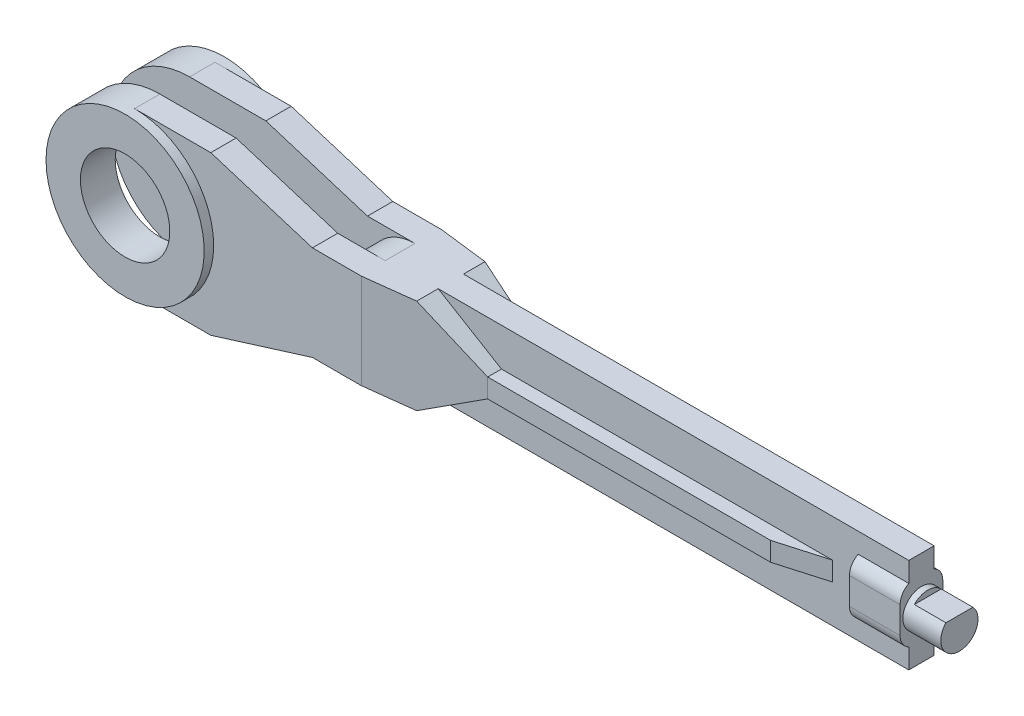
SolidWorks part; units mm, degrees
ref_plane "Front Plane" through (0, 0, 0) normal (0, 0, 1) x (1, 0, 0)
ref_plane "Top Plane" through (0, 0, 0) normal (0, 1, 0) x (1, 0, 0)
ref_plane "Right Plane" through (0, 0, 0) normal (1, 0, 0) x (0, 0, -1)
sketch "Sketch1" plane through (0, 0, 0) normal (0, 0, 1) x (1, 0, 0)
  line L0 (0, 12.5) -> (12.0413, 12.5)
  line L1 (12.0413, 12.5) -> (28.1062, 7.5)
  line L5 (28.1062, -7.5) -> (12.0413, -12.5)
  line L6 (12.0413, -12.5) -> (0, -12.5)
  line L7 (0, 0) -> (28.1062, 0) construction
  line L8 (28.1062, 7.5) -> (28.1062, -7.5)
  circle A0 centre (0, 0) radius 7.0625
  arc A1 (0, 12.5) -> (0, -12.5) centre (0, 0) ccw
  dimension "D1" = 14.125
  dimension "D2" = 25
  dimension "D3" = 15
extrude "Boss-Extrude1" add sketch "Sketch1" along normal blind 4
ref_plane "Plane1" through (0, 0, -2.35) normal (0, 0, -1) x (-1, 0, 0)
sketch "Sketch5" plane through (0, 0, 4) normal (0, 0, 1) x (1, 0, 0)
  line L0 (28.1062, 7.5) -> (28.1062, -7.5)
  line L1 (28.1062, 7.5) -> (53.6281, 7.5)
  line L3 (28.1062, -7.5) -> (53.6281, -7.5)
  line L4 (53.6281, 7.5) -> (53.6281, -7.5)
extrude "Boss-Extrude2" add sketch "Sketch5" against normal blind 12.7
mirror "Mirror1" about plane through (0, 0, -2.35) normal (0, 0, -1) of "Boss-Extrude1"
fillet "Fillet1" radius 7.5 2 edges at (28.1062, -7.5, -2.35) (28.1062, 7.5, -2.35)
sketch "Sketch6" plane through (0, 0, -2.35) normal (0, 0, -1) x (-1, 0, 0)
  line L0 (-28.1062, -7.5) -> (-53.6281, -7.5) construction
  line L1 (-53.6281, 7.5) -> (-118, 7.5)
  line L2 (-53.6281, 7.5) -> (-53.6281, -7.5)
  line L3 (-53.6281, -7.5) -> (-118, -7.5)
  line L4 (-118, 7.5) -> (-118, -7.5)
  point P8 (-118, 0)
  dimension "D1" = 118
extrude "Boss-Extrude3" add sketch "Sketch6" along normal mid plane 4
chamfer "Chamfer1" distance 10 distance2 6 2 edges at (53.6281, 7.5, 1.825) (53.6281, 7.5, -6.525) first distance on face at (52.8458, 7.5, -2.35)
chamfer "Chamfer2" distance 6 distance2 10 2 edges at (53.6281, -7.5, 1.825) (53.6281, -7.5, -6.525) first distance on face at (53.6281, -3, 1.825) first distance on face at (53.6281, -3, -6.525)
sketch "Sketch8" plane through (118, 0, 0) normal (1, 0, 0) x (0, 0, -1)
  line L0 (2.35, -16.9531) -> (2.35, 16.9531) construction
  circle A0 centre (2.35, 0) radius 2.9375
  dimension "D1" = 5.875
extrude "Boss-Extrude4" add sketch "Sketch8" along normal blind 6
sketch "Sketch9" plane through (0, 0, 0) normal (0, 1, 0) x (1, 0, 0)
  line L0 (53.6281, 8.7) -> (53.6281, 4.35) construction
  line L1 (53.6281, 6.525) -> (98.3499, 6.525)
  line L2 (53.6281, 6.525) -> (53.6281, -1.825)
  line L3 (53.6281, -1.825) -> (98.3499, -1.825)
  line L5 (92.9263, 2.35) -> (50092.9263, 2.35) construction
  line L6 (16.9531, 2.35) -> (-16.9531, 2.35) construction
  line L7 (98.3499, 6.525) -> (112.8561, 2.35)
  line L8 (112.8561, 2.35) -> (98.3499, -1.825)
extrude "Boss-Extrude5" add sketch "Sketch9" along normal mid plane 3
sketch "Sketch10" plane through (0, 0, 0) normal (0, 1, 0) x (1, 0, 0)
  line L0 (53.6281, 6.525) -> (35.8429, 8.7)
  line L1 (35.8429, 8.7) -> (53.6281, 8.7)
  line L2 (43.6281, 8.7) -> (53.6281, 8.7) construction
  line L3 (53.6281, 8.7) -> (53.6281, 6.525)
  line L4 (53.6281, -1.825) -> (35.8429, -4)
  line L5 (35.8429, -4) -> (53.6281, -4)
  line L6 (53.6281, -4) -> (53.6281, -1.825)
extrude "Cut-Extrude1" cut sketch "Sketch10" against normal mid plane 15
sketch "Sketch11" plane through (118, 0, 0) normal (-1, 0, 0) x (0, 0, 1)
  line L5 (-5.7213, -4.3444) -> (1.0213, -4.3444)
  line L6 (-5.7213, -4.3444) -> (-5.7213, 4.3444)
  line L7 (-5.7213, 4.3444) -> (1.0213, 4.3444)
  line L8 (1.0213, -4.3444) -> (1.0213, 4.3444)
extrude "Boss-Extrude7" add sketch "Sketch11" along normal blind 8
fillet "Fillet2" radius 2.5 4 edges at (114, 4.3444, 1.0213) (114, -4.3444, 1.0213) (114, 4.3444, -5.7213) (114, -4.3444, -5.7213)
sketch "Sketch12" plane through (0, 0, -8.7) normal (0, 0, -1) x (-1, 0, 0)
  circle A0 centre (0, 0) radius 7.0625 construction
  circle A1 centre (0, 0) radius 7.0625
  circle A2 centre (0, 0) radius 12.5
extrude "Boss-Extrude8" add sketch "Sketch12" along normal blind 1.5
mirror "Mirror2" about plane through (0, 0, -2.35) normal (0, 0, -1) of "Boss-Extrude8"
sketch "Sketch13" plane through (124, 0, 0) normal (1, 0, 0) x (0, 0, -1)
  line L0 (4.4765, 2.0266) -> (0.2235, 2.0266)
  circle A1 centre (2.35, 0) radius 2.9375
  arc A2 (4.4765, 2.0266) -> (0.2235, 2.0266) centre (2.35, 0) ccw
  dimension "D1" = 0
extrude "Cut-Extrude2" cut sketch "Sketch13" against normal blind 5
